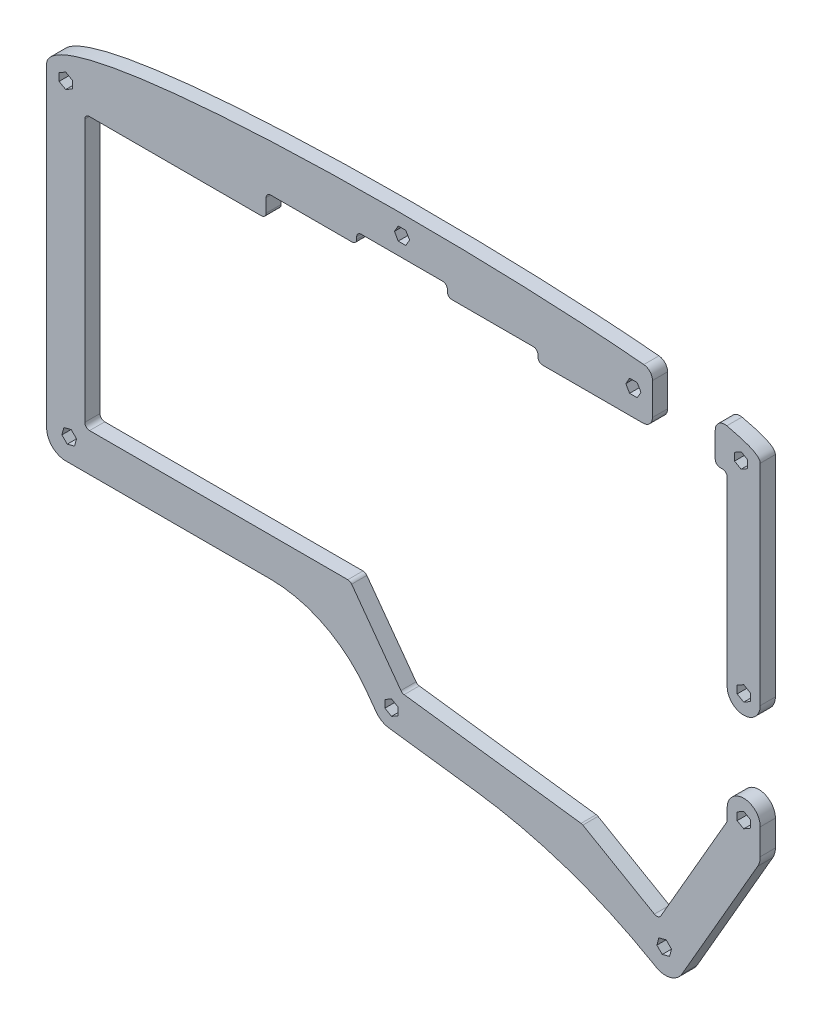
SolidWorks part; units mm, degrees
ref_plane "Front Plane" through (0, 0, 0) normal (0, 0, 1) x (1, 0, 0)
ref_plane "Top Plane" through (0, 0, 0) normal (0, 1, 0) x (1, 0, 0)
ref_plane "Right Plane" through (0, 0, 0) normal (1, 0, 0) x (0, 0, -1)
sketch "Model" plane through (0, 0, 0) normal (0, 0, 1) x (1, 0, 0)
  line L0 (-21.8431, 7.4481) -> (-8.6148, 30.3792)
  line L1 (-38.0636, 15.3297) -> (-23.771, 7.0696)
  line L2 (-75.3888, 20.2293) -> (-38.7189, 15.4592)
  line L3 (-86.2854, 34.8343) -> (-75.7419, 20.3766)
  line L4 (-29.1405, 92.9799) -> (-29.1405, 91.7303)
  line L5 (-8.8891, 91.2299) -> (-28.6402, 91.2299)
  line L6 (-8.3888, 90.7295) -> (-8.3888, 31.2555)
  line L7 (-86.6385, 34.9791) -> (-141.6396, 34.9791)
  line L8 (-142.1399, 90.7295) -> (-142.1399, 35.4795)
  line L9 (-104.6394, 91.2299) -> (-141.6396, 91.2299)
  line L10 (-104.139, 95.4793) -> (-104.139, 91.7303)
  line L11 (-85.6402, 95.9797) -> (-103.6387, 95.9797)
  line L12 (-85.1399, 97.7297) -> (-85.1399, 96.4801)
  line L13 (-67.6393, 98.2301) -> (-84.6395, 98.2301)
  line L14 (-67.1389, 96.4801) -> (-67.1389, 97.7297)
  line L15 (-48.6401, 95.9797) -> (-66.6385, 95.9797)
  line L16 (-48.1397, 93.9807) -> (-48.1397, 95.4793)
  line L17 (-29.6384, 93.4803) -> (-47.6393, 93.4803)
  line L18 (135.1563, 30.6526) -> (116.2359, 41.5721)
  line L19 (123.1828, 7.2669) -> (135.5373, 28.7222)
  line L20 (106.9623, 15.1485) -> (121.2549, 6.8884)
  line L21 (69.6371, 20.0481) -> (106.307, 15.278)
  line L22 (58.7405, 34.6531) -> (69.284, 20.1955)
  line L23 (115.8854, 92.7987) -> (115.8828, 42.2376)
  line L24 (58.3874, 34.7979) -> (3.3863, 34.7979)
  line L25 (2.886, 90.5483) -> (2.886, 35.2983)
  line L26 (40.3865, 91.0487) -> (3.3863, 91.0487)
  line L27 (40.8869, 95.2981) -> (40.8869, 91.5491)
  line L28 (59.3857, 95.7985) -> (41.3872, 95.7985)
  line L29 (59.886, 97.5485) -> (59.886, 96.2989)
  line L30 (77.3866, 98.0489) -> (60.3864, 98.0489)
  line L31 (77.887, 96.2989) -> (77.887, 97.5485)
  line L32 (96.3858, 95.7985) -> (78.3874, 95.7985)
  line L33 (96.8862, 93.7995) -> (96.8862, 95.2981)
  line L34 (115.3875, 93.2991) -> (97.3866, 93.2991)
  line L35 (20.1915, -96.2476) -> (6.9631, -73.3165)
  line L36 (36.4119, -88.366) -> (22.1193, -96.6261)
  line L37 (73.7371, -83.4663) -> (37.0672, -88.2365)
  line L38 (84.6337, -68.8614) -> (74.0902, -83.319)
  line L39 (27.4889, -10.7157) -> (27.4889, -11.9654)
  line L40 (7.2375, -12.4658) -> (26.9885, -12.4658)
  line L41 (6.7371, -12.9662) -> (6.7371, -72.4402)
  line L42 (84.9868, -68.7166) -> (139.9879, -68.7166)
  line L43 (140.4883, -12.9662) -> (140.4883, -68.2162)
  line L44 (102.9878, -12.4658) -> (139.9879, -12.4658)
  line L45 (102.4874, -8.2164) -> (102.4874, -11.9654)
  line L46 (83.9886, -7.716) -> (101.987, -7.716)
  line L47 (83.4882, -5.9659) -> (83.4882, -7.2156)
  line L48 (65.9876, -5.4656) -> (82.9878, -5.4656)
  line L49 (65.4872, -7.2156) -> (65.4872, -5.9659)
  line L50 (46.9884, -7.716) -> (64.9869, -7.716)
  line L51 (46.488, -9.715) -> (46.488, -8.2164)
  line L52 (27.9867, -10.2154) -> (45.9877, -10.2154)
  line L53 (-136.808, -73.043) -> (-117.8876, -62.1236)
  line L54 (-124.8344, -96.4288) -> (-137.189, -74.9734)
  line L55 (-108.614, -88.5472) -> (-122.9066, -96.8073)
  line L56 (-71.2888, -83.6475) -> (-107.9587, -88.4176)
  line L57 (-60.3922, -69.0425) -> (-70.9357, -83.5002)
  line L58 (-117.537, -10.8969) -> (-117.5345, -61.4581)
  line L59 (-60.0391, -68.8978) -> (-5.038, -68.8978)
  line L60 (-4.5376, -13.1474) -> (-4.5376, -68.3974)
  line L61 (-42.0381, -12.647) -> (-5.038, -12.647)
  line L62 (-42.5385, -8.3976) -> (-42.5385, -12.1466)
  line L63 (-61.0373, -7.8972) -> (-43.0389, -7.8972)
  line L64 (-61.5377, -6.1471) -> (-61.5377, -7.3968)
  line L65 (-79.0383, -5.6467) -> (-62.0381, -5.6467)
  line L66 (-79.5387, -7.3968) -> (-79.5387, -6.1471)
  line L67 (-98.0375, -7.8972) -> (-80.039, -7.8972)
  line L68 (-98.5378, -9.8962) -> (-98.5378, -8.3976)
  line L69 (-117.0392, -10.3965) -> (-99.0382, -10.3965)
  line L70 (138.9148, 92.1117) -> (138.9148, 33.3582)
  line L71 (138.1649, 32.9251) -> (119.446, 43.7282)
  line L72 (119.196, 44.1613) -> (119.196, 92.1092)
  line L73 (119.6959, 92.6092) -> (138.4148, 92.6117)
  line L74 (-140.5665, -11.584) -> (-140.5665, -70.3375)
  line L75 (-139.8166, -70.7706) -> (-121.0977, -59.9674)
  line L76 (-120.8476, -59.5344) -> (-120.8476, -11.5865)
  line L77 (-121.3476, -11.0865) -> (-140.0664, -11.084)
  line L78 (18.8966, 74.9256) -> (4.8966, 74.9256)
  line L79 (4.8966, 74.9256) -> (4.8966, 88.9256)
  line L80 (4.8966, 88.9256) -> (18.8966, 88.9256)
  line L81 (18.8966, 88.9256) -> (18.8966, 74.9256)
  line L82 (18.8966, 55.9256) -> (4.8966, 55.9256)
  line L83 (4.8966, 55.9256) -> (4.8966, 69.9256)
  line L84 (4.8966, 69.9256) -> (18.8966, 69.9256)
  line L85 (18.8966, 69.9256) -> (18.8966, 55.9256)
  line L86 (18.8966, 36.9256) -> (4.8966, 36.9256)
  line L87 (4.8966, 36.9256) -> (4.8966, 50.9256)
  line L88 (4.8966, 50.9256) -> (18.8966, 50.9256)
  line L89 (18.8966, 50.9256) -> (18.8966, 36.9256)
  line L90 (37.8948, 74.9262) -> (23.8948, 74.9262)
  line L91 (23.8948, 74.9262) -> (23.8948, 88.9262)
  line L92 (23.8948, 88.9262) -> (37.8948, 88.9262)
  line L93 (37.8948, 88.9262) -> (37.8948, 74.9262)
  line L94 (37.8948, 55.9262) -> (23.8948, 55.9262)
  line L95 (23.8948, 55.9262) -> (23.8948, 69.9262)
  line L96 (23.8948, 69.9262) -> (37.8948, 69.9262)
  line L97 (37.8948, 69.9262) -> (37.8948, 55.9262)
  line L98 (37.8948, 36.9262) -> (23.8948, 36.9262)
  line L99 (23.8948, 36.9262) -> (23.8948, 50.9262)
  line L100 (23.8948, 50.9262) -> (37.8948, 50.9262)
  line L101 (37.8948, 50.9262) -> (37.8948, 36.9262)
  line L102 (56.895, 79.671) -> (42.895, 79.671)
  line L103 (42.895, 79.671) -> (42.895, 93.671)
  line L104 (42.895, 93.671) -> (56.895, 93.671)
  line L105 (56.895, 93.671) -> (56.895, 79.671)
  line L106 (56.895, 60.6711) -> (42.895, 60.6711)
  line L107 (42.895, 60.6711) -> (42.895, 74.6711)
  line L108 (42.895, 74.6711) -> (56.895, 74.6711)
  line L109 (56.895, 74.6711) -> (56.895, 60.6711)
  line L110 (56.895, 41.6711) -> (42.895, 41.6711)
  line L111 (42.895, 41.6711) -> (42.895, 55.6711)
  line L112 (42.895, 55.6711) -> (56.895, 55.6711)
  line L113 (56.895, 55.6711) -> (56.895, 41.6711)
  line L114 (75.897, 82.0499) -> (61.897, 82.0499)
  line L115 (61.897, 82.0499) -> (61.897, 96.0499)
  line L116 (61.897, 96.0499) -> (75.897, 96.0499)
  line L117 (75.897, 96.0499) -> (75.897, 82.0499)
  line L118 (75.897, 63.0499) -> (61.897, 63.0499)
  line L119 (61.897, 63.0499) -> (61.897, 77.0499)
  line L120 (61.897, 77.0499) -> (75.897, 77.0499)
  line L121 (75.897, 77.0499) -> (75.897, 63.0499)
  line L122 (75.897, 44.0499) -> (61.897, 44.0499)
  line L123 (61.897, 44.0499) -> (61.897, 58.0499)
  line L124 (61.897, 58.0499) -> (75.897, 58.0499)
  line L125 (75.897, 58.0499) -> (75.897, 44.0499)
  line L126 (94.8982, 79.6753) -> (80.8982, 79.6753)
  line L127 (80.8982, 79.6753) -> (80.8982, 93.6753)
  line L128 (80.8982, 93.6753) -> (94.8982, 93.6753)
  line L129 (94.8982, 93.6753) -> (94.8982, 79.6753)
  line L130 (94.8982, 60.6753) -> (80.8982, 60.6753)
  line L131 (80.8982, 60.6753) -> (80.8982, 74.6753)
  line L132 (80.8982, 74.6753) -> (94.8982, 74.6753)
  line L133 (94.8982, 74.6753) -> (94.8982, 60.6753)
  line L134 (94.8982, 41.6753) -> (80.8982, 41.6753)
  line L135 (80.8982, 41.6753) -> (80.8982, 55.6753)
  line L136 (80.8982, 55.6753) -> (94.8982, 55.6753)
  line L137 (94.8982, 55.6753) -> (94.8982, 41.6753)
  line L138 (113.9, 77.2905) -> (99.9, 77.2905)
  line L139 (99.9, 77.2905) -> (99.9, 91.2905)
  line L140 (99.9, 91.2905) -> (113.9, 91.2905)
  line L141 (113.9, 91.2905) -> (113.9, 77.2905)
  line L142 (113.9, 58.2905) -> (99.9, 58.2905)
  line L143 (99.9, 58.2905) -> (99.9, 72.2905)
  line L144 (99.9, 72.2905) -> (113.9, 72.2905)
  line L145 (113.9, 72.2905) -> (113.9, 58.2905)
  line L146 (113.9, 39.2905) -> (99.9, 39.2905)
  line L147 (99.9, 39.2905) -> (99.9, 53.2905)
  line L148 (99.9, 53.2905) -> (113.9, 53.2905)
  line L149 (113.9, 53.2905) -> (113.9, 39.2905)
  line L150 (85.4166, 22.0174) -> (71.4166, 22.0174)
  line L151 (71.4166, 22.0174) -> (71.4166, 36.0174)
  line L152 (71.4166, 36.0174) -> (85.4166, 36.0174)
  line L153 (85.4166, 36.0174) -> (85.4166, 22.0174)
  line L154 (104.3289, 17.734) -> (90.806, 21.3575)
  line L155 (90.806, 21.3575) -> (94.4294, 34.8805)
  line L156 (94.4294, 34.8805) -> (107.9524, 31.257)
  line L157 (107.9524, 31.257) -> (104.3289, 17.734)
  line L158 (124.1994, 13.0049) -> (112.075, 20.0049)
  line L159 (112.075, 20.0049) -> (119.075, 32.1293)
  line L160 (119.075, 32.1293) -> (131.1994, 25.1293)
  line L161 (131.1994, 25.1293) -> (124.1994, 13.0049)
  line L162 (-20.5483, -28.7701) -> (-6.5483, -28.7701)
  line L163 (-6.5483, -28.7701) -> (-6.5483, -14.7701)
  line L164 (-6.5483, -14.7701) -> (-20.5483, -14.7701)
  line L165 (-20.5483, -14.7701) -> (-20.5483, -28.7701)
  line L166 (-20.5483, -47.7701) -> (-6.5483, -47.7701)
  line L167 (-6.5483, -47.7701) -> (-6.5483, -33.7701)
  line L168 (-6.5483, -33.7701) -> (-20.5483, -33.7701)
  line L169 (-20.5483, -33.7701) -> (-20.5483, -47.7701)
  line L170 (-20.5483, -66.7701) -> (-6.5483, -66.7701)
  line L171 (-6.5483, -66.7701) -> (-6.5483, -52.7701)
  line L172 (-6.5483, -52.7701) -> (-20.5483, -52.7701)
  line L173 (-20.5483, -52.7701) -> (-20.5483, -66.7701)
  line L174 (-39.5464, -28.7694) -> (-25.5464, -28.7694)
  line L175 (-25.5464, -28.7694) -> (-25.5464, -14.7694)
  line L176 (-25.5464, -14.7694) -> (-39.5464, -14.7694)
  line L177 (-39.5464, -14.7694) -> (-39.5464, -28.7694)
  line L178 (-39.5464, -47.7694) -> (-25.5464, -47.7694)
  line L179 (-25.5464, -47.7694) -> (-25.5464, -33.7694)
  line L180 (-25.5464, -33.7694) -> (-39.5464, -33.7694)
  line L181 (-39.5464, -33.7694) -> (-39.5464, -47.7694)
  line L182 (-39.5464, -66.7694) -> (-25.5464, -66.7694)
  line L183 (-25.5464, -66.7694) -> (-25.5464, -52.7694)
  line L184 (-25.5464, -52.7694) -> (-39.5464, -52.7694)
  line L185 (-39.5464, -52.7694) -> (-39.5464, -66.7694)
  line L186 (-58.5467, -24.0246) -> (-44.5467, -24.0246)
  line L187 (-44.5467, -24.0246) -> (-44.5467, -10.0246)
  line L188 (-44.5467, -10.0246) -> (-58.5467, -10.0246)
  line L189 (-58.5467, -10.0246) -> (-58.5467, -24.0246)
  line L190 (-58.5467, -43.0246) -> (-44.5467, -43.0246)
  line L191 (-44.5467, -43.0246) -> (-44.5467, -29.0246)
  line L192 (-44.5467, -29.0246) -> (-58.5467, -29.0246)
  line L193 (-58.5467, -29.0246) -> (-58.5467, -43.0246)
  line L194 (-58.5467, -62.0246) -> (-44.5467, -62.0246)
  line L195 (-44.5467, -62.0246) -> (-44.5467, -48.0246)
  line L196 (-44.5467, -48.0246) -> (-58.5467, -48.0246)
  line L197 (-58.5467, -48.0246) -> (-58.5467, -62.0246)
  line L198 (-77.5486, -21.6458) -> (-63.5486, -21.6458)
  line L199 (-63.5486, -21.6458) -> (-63.5486, -7.6458)
  line L200 (-63.5486, -7.6458) -> (-77.5486, -7.6458)
  line L201 (-77.5486, -7.6458) -> (-77.5486, -21.6458)
  line L202 (-77.5486, -40.6458) -> (-63.5486, -40.6458)
  line L203 (-63.5486, -40.6458) -> (-63.5486, -26.6458)
  line L204 (-63.5486, -26.6458) -> (-77.5486, -26.6458)
  line L205 (-77.5486, -26.6458) -> (-77.5486, -40.6458)
  line L206 (-77.5486, -59.6458) -> (-63.5486, -59.6458)
  line L207 (-63.5486, -59.6458) -> (-63.5486, -45.6458)
  line L208 (-63.5486, -45.6458) -> (-77.5486, -45.6458)
  line L209 (-77.5486, -45.6458) -> (-77.5486, -59.6458)
  line L210 (-96.5499, -24.0204) -> (-82.5499, -24.0204)
  line L211 (-82.5499, -24.0204) -> (-82.5499, -10.0204)
  line L212 (-82.5499, -10.0204) -> (-96.5499, -10.0204)
  line L213 (-96.5499, -10.0204) -> (-96.5499, -24.0204)
  line L214 (-96.5499, -43.0203) -> (-82.5499, -43.0203)
  line L215 (-82.5499, -43.0203) -> (-82.5499, -29.0203)
  line L216 (-82.5499, -29.0203) -> (-96.5499, -29.0203)
  line L217 (-96.5499, -29.0203) -> (-96.5499, -43.0203)
  line L218 (-96.5499, -62.0203) -> (-82.5499, -62.0203)
  line L219 (-82.5499, -62.0203) -> (-82.5499, -48.0203)
  line L220 (-82.5499, -48.0203) -> (-96.5499, -48.0203)
  line L221 (-96.5499, -48.0203) -> (-96.5499, -62.0203)
  line L222 (-115.5516, -26.4052) -> (-101.5516, -26.4052)
  line L223 (-101.5516, -26.4052) -> (-101.5516, -12.4052)
  line L224 (-101.5516, -12.4052) -> (-115.5516, -12.4052)
  line L225 (-115.5516, -12.4052) -> (-115.5516, -26.4052)
  line L226 (-115.5516, -45.4052) -> (-101.5516, -45.4052)
  line L227 (-101.5516, -45.4052) -> (-101.5516, -31.4052)
  line L228 (-101.5516, -31.4052) -> (-115.5516, -31.4052)
  line L229 (-115.5516, -31.4052) -> (-115.5516, -45.4052)
  line L230 (-115.5516, -64.4052) -> (-101.5516, -64.4052)
  line L231 (-101.5516, -64.4052) -> (-101.5516, -50.4052)
  line L232 (-101.5516, -50.4052) -> (-115.5516, -50.4052)
  line L233 (-115.5516, -50.4052) -> (-115.5516, -64.4052)
  line L234 (-87.0683, -81.6783) -> (-73.0683, -81.6783)
  line L235 (-73.0683, -81.6783) -> (-73.0683, -67.6783)
  line L236 (-73.0683, -67.6783) -> (-87.0683, -67.6783)
  line L237 (-87.0683, -67.6783) -> (-87.0683, -81.6783)
  line L238 (-105.9806, -85.9616) -> (-92.4576, -82.3382)
  line L239 (-92.4576, -82.3382) -> (-96.0811, -68.8152)
  line L240 (-96.0811, -68.8152) -> (-109.6041, -72.4387)
  line L241 (-109.6041, -72.4387) -> (-105.9806, -85.9616)
  line L242 (-125.851, -90.6908) -> (-113.7267, -83.6908)
  line L243 (-113.7267, -83.6908) -> (-120.7267, -71.5664)
  line L244 (-120.7267, -71.5664) -> (-132.851, -78.5664)
  line L245 (-132.851, -78.5664) -> (-125.851, -90.6908)
  spline S0 degree 3 poles (-8.6153, 30.3807) (-8.4626, 30.6458) (-8.3842, 30.9472) (-8.3882, 31.2532) knots 0 0 0 0 1 1 1 1
  spline S1 degree 3 poles (-21.8439, 7.4422) (-21.8429, 7.4437) (-21.8419, 7.4453) (-21.8408, 7.4468) knots 1 1 1 1 2 2 2 2
  spline S2 degree 3 poles (-23.769, 7.0673) (-23.1339, 6.6392) (-22.272, 6.8071) (-21.8439, 7.4422) knots 0 0 0 0 1 1 1 1
  spline S3 degree 3 poles (-38.063, 15.3284) (-38.2765, 15.3928) (-38.4957, 15.4362) (-38.7176, 15.4579) knots 0 0 0 0 1 1 1 1
  spline S4 degree 3 poles (-75.7416, 20.3746) (-75.6478, 20.2809) (-75.5206, 20.2283) (-75.3881, 20.2283) knots 0 0 0 0 1 1 1 1
  spline S5 degree 3 poles (-29.1383, 92.9782) (-29.1382, 93.2543) (-29.362, 93.4782) (-29.6381, 93.4783) knots 0 0 0 0 1 1 1 1
  spline S6 degree 3 poles (-29.1383, 91.7282) (-29.1383, 91.4521) (-28.9145, 91.2282) (-28.6384, 91.2281) (-28.6383, 91.2281) (-28.6382, 91.2281) (-28.6381, 91.2281) knots 0 0 0 0 1 1 1 2 2 2 2
  spline S7 degree 3 poles (-86.2846, 34.8318) (-86.3784, 34.9256) (-86.5056, 34.9783) (-86.6385, 34.9791) knots 0 0 0 0 1 1 1 1
  spline S8 degree 3 poles (-142.1382, 35.4782) (-142.1381, 35.2021) (-141.9142, 34.9783) (-141.6381, 34.9783) knots 0 0 0 0 1 1 1 1
  spline S9 degree 3 poles (-141.638, 91.2281) (-141.9142, 91.2282) (-142.1381, 91.0044) (-142.1382, 90.7282) knots 0 0 0 0 1 1 1 1
  spline S10 degree 3 poles (-104.6382, 91.2281) (-104.362, 91.228) (-104.1381, 91.4518) (-104.138, 91.728) (-104.138, 91.7281) (-104.138, 91.7281) (-104.138, 91.7282) knots 0 0 0 0 1 1 1 2 2 2 2
  spline S11 degree 3 poles (-103.6382, 95.9781) (-103.9142, 95.9781) (-104.138, 95.7543) (-104.138, 95.4783) knots 0 0 0 0 1 1 1 1
  spline S12 degree 3 poles (-85.6382, 95.9781) (-85.3621, 95.9781) (-85.1382, 96.2019) (-85.1381, 96.478) (-85.1381, 96.4781) (-85.1381, 96.4782) (-85.1381, 96.4783) knots 0 0 0 0 1 1 1 2 2 2 2
  spline S13 degree 3 poles (-84.6382, 98.2283) (-84.9144, 98.2283) (-85.1382, 98.0044) (-85.1381, 97.7282) knots 0 0 0 0 1 1 1 1
  spline S14 degree 3 poles (-67.1381, 97.7282) (-67.1381, 98.0043) (-67.3619, 98.2283) (-67.638, 98.2283) knots 0 0 0 0 2 2 2 2
  spline S15 degree 3 poles (-67.1381, 96.4783) (-67.1382, 96.2021) (-66.9144, 95.9782) (-66.6383, 95.9781) (-66.6382, 95.9781) (-66.6381, 95.9781) (-66.638, 95.9781) knots 0 0 0 0 1 1 1 2 2 2 2
  spline S16 degree 3 poles (-48.1382, 95.4783) (-48.1383, 95.7543) (-48.362, 95.9781) (-48.6381, 95.9781) knots 0 0 0 0 1 1 1 1
  spline S17 degree 3 poles (-48.1382, 93.9782) (-48.1381, 93.702) (-47.9142, 93.4782) (-47.6381, 93.4783) knots 0 0 0 0 1 1 1 1
  spline S18 degree 3 poles (-8.3882, 90.7282) (-8.3883, 91.0043) (-8.6121, 91.228) (-8.8881, 91.2281) knots 0 0 0 0 1 1 1 1
  spline S19 degree 3 poles (115.8851, 42.2368) (115.8929, 41.9725) (116.0232, 41.7268) (116.2377, 41.5721) knots 0 0 0 0 1 1 1 1
  spline S20 degree 3 poles (135.163, 30.647) (135.1614, 30.648) (135.1599, 30.6491) (135.1583, 30.6501) knots 1 1 1 1 2 2 2 2
  spline S21 degree 3 poles (135.5373, 28.7222) (135.9659, 29.3571) (135.7981, 30.2189) (135.163, 30.647) knots 0 0 0 0 1 1 1 1
  spline S22 degree 3 poles (123.182, 7.261) (123.183, 7.2625) (123.184, 7.2641) (123.1851, 7.2656) knots 1 1 1 1 2 2 2 2
  spline S23 degree 3 poles (121.2569, 6.8861) (121.892, 6.4581) (122.7539, 6.6259) (123.182, 7.261) knots 0 0 0 0 1 1 1 1
  spline S24 degree 3 poles (106.9629, 15.1472) (106.7494, 15.2117) (106.5302, 15.255) (106.3083, 15.2768) knots 0 0 0 0 1 1 1 1
  spline S25 degree 3 poles (69.2843, 20.1934) (69.3781, 20.0997) (69.5053, 20.0471) (69.6378, 20.0471) knots 0 0 0 0 1 1 1 1
  spline S26 degree 3 poles (115.8876, 92.797) (115.8877, 93.0731) (115.6639, 93.297) (115.3878, 93.2971) knots 0 0 0 0 1 1 1 1
  spline S27 degree 3 poles (58.7413, 34.6506) (58.6475, 34.7444) (58.5203, 34.7971) (58.3874, 34.7979) knots 0 0 0 0 1 1 1 1
  spline S28 degree 3 poles (2.8877, 35.297) (2.8878, 35.0209) (3.1117, 34.7971) (3.3878, 34.7971) knots 0 0 0 0 1 1 1 1
  spline S29 degree 3 poles (3.3879, 91.0469) (3.1117, 91.047) (2.8878, 90.8232) (2.8877, 90.547) knots 0 0 0 0 1 1 1 1
  spline S30 degree 3 poles (40.3877, 91.0469) (40.6639, 91.0468) (40.8878, 91.2706) (40.8879, 91.5468) (40.8879, 91.5469) (40.8879, 91.5469) (40.8879, 91.547) knots 0 0 0 0 1 1 1 2 2 2 2
  spline S31 degree 3 poles (41.3877, 95.797) (41.1117, 95.7969) (40.8879, 95.5731) (40.8879, 95.2971) knots 0 0 0 0 1 1 1 1
  spline S32 degree 3 poles (59.3877, 95.797) (59.6638, 95.7969) (59.8877, 96.0207) (59.8878, 96.2968) (59.8878, 96.2969) (59.8878, 96.297) (59.8878, 96.2971) knots 0 0 0 0 1 1 1 2 2 2 2
  spline S33 degree 3 poles (60.3877, 98.0471) (60.1115, 98.0471) (59.8877, 97.8232) (59.8878, 97.547) knots 0 0 0 0 1 1 1 1
  spline S34 degree 3 poles (77.8878, 97.547) (77.8878, 97.8232) (77.664, 98.0471) (77.3879, 98.0471) knots 0 0 0 0 2 2 2 2
  spline S35 degree 3 poles (77.8878, 96.2971) (77.8877, 96.0209) (78.1115, 95.797) (78.3876, 95.797) (78.3877, 95.797) (78.3878, 95.797) (78.3879, 95.797) knots 0 0 0 0 1 1 1 2 2 2 2
  spline S36 degree 3 poles (96.8877, 95.2971) (96.8876, 95.5731) (96.6639, 95.7969) (96.3878, 95.797) knots 0 0 0 0 1 1 1 1
  spline S37 degree 3 poles (96.8877, 93.797) (96.8878, 93.5208) (97.1117, 93.297) (97.3878, 93.2971) knots 0 0 0 0 1 1 1 1
  spline S38 degree 3 poles (6.9637, -73.315) (6.8109, -73.0499) (6.7325, -72.7484) (6.7366, -72.4425) knots 0 0 0 0 1 1 1 1
  spline S39 degree 3 poles (20.1923, -96.2535) (20.1912, -96.252) (20.1902, -96.2504) (20.1892, -96.2489) knots 1 1 1 1 2 2 2 2
  spline S40 degree 3 poles (22.1173, -96.6284) (21.4822, -97.0564) (20.6203, -96.8886) (20.1923, -96.2535) knots 0 0 0 0 1 1 1 1
  spline S41 degree 3 poles (36.4114, -88.3673) (36.6248, -88.3028) (36.844, -88.2594) (37.0659, -88.2377) knots 0 0 0 0 1 1 1 1
  spline S42 degree 3 poles (74.0899, -83.3211) (73.9962, -83.4148) (73.869, -83.4674) (73.7364, -83.4674) knots 0 0 0 0 1 1 1 1
  spline S43 degree 3 poles (27.4866, -10.7175) (27.4865, -10.4414) (27.7103, -10.2175) (27.9865, -10.2174) knots 0 0 0 0 1 1 1 1
  spline S44 degree 3 poles (27.4866, -11.9674) (27.4866, -12.2436) (27.2628, -12.4675) (26.9867, -12.4676) (26.9866, -12.4676) (26.9865, -12.4676) (26.9865, -12.4676) knots 0 0 0 0 1 1 1 2 2 2 2
  spline S45 degree 3 poles (84.633, -68.8639) (84.7267, -68.7701) (84.8539, -68.7174) (84.9868, -68.7166) knots 0 0 0 0 1 1 1 1
  spline S46 degree 3 poles (140.4865, -68.2175) (140.4864, -68.4936) (140.2625, -68.7174) (139.9864, -68.7173) knots 0 0 0 0 1 1 1 1
  spline S47 degree 3 poles (139.9864, -12.4676) (140.2625, -12.4675) (140.4864, -12.6913) (140.4865, -12.9674) knots 0 0 0 0 1 1 1 1
  spline S48 degree 3 poles (102.9865, -12.4676) (102.7103, -12.4676) (102.4864, -12.2438) (102.4864, -11.9677) (102.4864, -11.9676) (102.4864, -11.9675) (102.4864, -11.9674) knots 0 0 0 0 1 1 1 2 2 2 2
  spline S49 degree 3 poles (101.9865, -7.7175) (102.2625, -7.7176) (102.4863, -7.9413) (102.4864, -8.2174) knots 0 0 0 0 1 1 1 1
  spline S50 degree 3 poles (83.9865, -7.7175) (83.7104, -7.7176) (83.4865, -7.4938) (83.4864, -7.2176) (83.4864, -7.2176) (83.4864, -7.2175) (83.4864, -7.2174) knots 0 0 0 0 1 1 1 2 2 2 2
  spline S51 degree 3 poles (82.9865, -5.4673) (83.2627, -5.4674) (83.4865, -5.6913) (83.4864, -5.9675) knots 0 0 0 0 1 1 1 1
  spline S52 degree 3 poles (65.4865, -5.9675) (65.4864, -5.6913) (65.7102, -5.4674) (65.9863, -5.4673) knots 0 0 0 0 2 2 2 2
  spline S53 degree 3 poles (65.4865, -7.2174) (65.4865, -7.4935) (65.2627, -7.7174) (64.9866, -7.7175) (64.9865, -7.7175) (64.9864, -7.7175) (64.9863, -7.7175) knots 0 0 0 0 1 1 1 2 2 2 2
  spline S54 degree 3 poles (46.4865, -8.2174) (46.4866, -7.9413) (46.7103, -7.7176) (46.9864, -7.7175) knots 0 0 0 0 1 1 1 1
  spline S55 degree 3 poles (46.4865, -9.7175) (46.4865, -9.9937) (46.2625, -10.2175) (45.9864, -10.2174) knots 0 0 0 0 1 1 1 1
  spline S56 degree 3 poles (6.7366, -12.9674) (6.7366, -12.6914) (6.9604, -12.4676) (7.2365, -12.4676) knots 0 0 0 0 1 1 1 1
  spline S57 degree 3 poles (-117.5368, -61.4589) (-117.5446, -61.7232) (-117.6748, -61.9689) (-117.8893, -62.1236) knots 0 0 0 0 1 1 1 1
  spline S58 degree 3 poles (-136.8146, -73.0487) (-136.8131, -73.0476) (-136.8116, -73.0466) (-136.81, -73.0456) knots 1 1 1 1 2 2 2 2
  spline S59 degree 3 poles (-137.189, -74.9734) (-137.6176, -74.3386) (-137.4497, -73.4767) (-136.8146, -73.0487) knots 0 0 0 0 1 1 1 1
  spline S60 degree 3 poles (-124.8336, -96.4347) (-124.8347, -96.4331) (-124.8357, -96.4316) (-124.8367, -96.4301) knots 1 1 1 1 2 2 2 2
  spline S61 degree 3 poles (-122.9086, -96.8095) (-123.5437, -97.2376) (-124.4056, -97.0698) (-124.8336, -96.4347) knots 0 0 0 0 1 1 1 1
  spline S62 degree 3 poles (-108.6145, -88.5485) (-108.4011, -88.484) (-108.1819, -88.4406) (-107.96, -88.4189) knots 0 0 0 0 1 1 1 1
  spline S63 degree 3 poles (-70.936, -83.5022) (-71.0297, -83.596) (-71.1569, -83.6486) (-71.2895, -83.6485) knots 0 0 0 0 1 1 1 1
  spline S64 degree 3 poles (-117.5393, -10.8987) (-117.5394, -10.6226) (-117.3156, -10.3987) (-117.0394, -10.3986) knots 0 0 0 0 1 1 1 1
  spline S65 degree 3 poles (-60.3929, -69.0451) (-60.2992, -68.9513) (-60.172, -68.8986) (-60.0391, -68.8978) knots 0 0 0 0 1 1 1 1
  spline S66 degree 3 poles (-4.5394, -68.3987) (-4.5395, -68.6748) (-4.7634, -68.8986) (-5.0395, -68.8985) knots 0 0 0 0 1 1 1 1
  spline S67 degree 3 poles (-5.0395, -12.6488) (-4.7634, -12.6487) (-4.5395, -12.8725) (-4.5394, -13.1486) knots 0 0 0 0 1 1 1 1
  spline S68 degree 3 poles (-42.0394, -12.6488) (-42.3156, -12.6488) (-42.5395, -12.425) (-42.5395, -12.1489) (-42.5395, -12.1488) (-42.5395, -12.1487) (-42.5395, -12.1486) knots 0 0 0 0 1 1 1 2 2 2 2
  spline S69 degree 3 poles (-43.0394, -7.8987) (-42.7634, -7.8988) (-42.5396, -8.1225) (-42.5395, -8.3986) knots 0 0 0 0 1 1 1 1
  spline S70 degree 3 poles (-61.0394, -7.8987) (-61.3155, -7.8988) (-61.5394, -7.675) (-61.5395, -7.3988) (-61.5395, -7.3988) (-61.5395, -7.3987) (-61.5395, -7.3986) knots 0 0 0 0 1 1 1 2 2 2 2
  spline S71 degree 3 poles (-62.0394, -5.6485) (-61.7632, -5.6486) (-61.5394, -5.8725) (-61.5395, -6.1486) knots 0 0 0 0 1 1 1 1
  spline S72 degree 3 poles (-79.5394, -6.1486) (-79.5395, -5.8725) (-79.3157, -5.6486) (-79.0396, -5.6485) knots 0 0 0 0 2 2 2 2
  spline S73 degree 3 poles (-79.5394, -7.3986) (-79.5394, -7.6747) (-79.7632, -7.8986) (-80.0393, -7.8987) (-80.0394, -7.8987) (-80.0395, -7.8987) (-80.0396, -7.8987) knots 0 0 0 0 1 1 1 2 2 2 2
  spline S74 degree 3 poles (-98.5394, -8.3986) (-98.5393, -8.1225) (-98.3156, -7.8988) (-98.0395, -7.8987) knots 0 0 0 0 1 1 1 1
  spline S75 degree 3 poles (-98.5394, -9.8987) (-98.5394, -10.1748) (-98.7634, -10.3986) (-99.0395, -10.3986) knots 0 0 0 0 1 1 1 1
  spline S76 degree 3 poles (-123.6381, 52.6314) (-124.2456, 52.6314) (-124.7381, 53.1239) (-124.7381, 53.7314) (-124.7381, 54.3389) (-124.2456, 54.8314) (-123.6381, 54.8314) knots 2 2 2 2 3 3 3 4 4 4 4
  spline S77 degree 3 poles (-123.6381, 54.8314) (-123.0306, 54.8314) (-122.5381, 54.3389) (-122.5381, 53.7314) (-122.5381, 53.1239) (-123.0306, 52.6314) (-123.6381, 52.6314) knots 0 0 0 0 1 1 1 2 2 2 2
  spline S78 degree 3 poles (-123.6381, 71.3814) (-124.2456, 71.3814) (-124.7381, 71.8739) (-124.7381, 72.4814) (-124.7381, 73.0889) (-124.2456, 73.5814) (-123.6381, 73.5814) knots 2 2 2 2 3 3 3 4 4 4 4
  spline S79 degree 3 poles (-123.6381, 73.5814) (-123.0306, 73.5814) (-122.5381, 73.0889) (-122.5381, 72.4814) (-122.5381, 71.8739) (-123.0306, 71.3814) (-123.6381, 71.3814) knots 0 0 0 0 1 1 1 2 2 2 2
  spline S80 degree 3 poles (-47.6381, 75.1312) (-48.2456, 75.1312) (-48.7381, 75.6237) (-48.7381, 76.2312) (-48.7381, 76.8387) (-48.2456, 77.3312) (-47.6381, 77.3312) knots 2 2 2 2 3 3 3 4 4 4 4
  spline S81 degree 3 poles (-47.6381, 77.3312) (-47.0306, 77.3312) (-46.5381, 76.8387) (-46.5381, 76.2312) (-46.5381, 75.6237) (-47.0306, 75.1312) (-47.6381, 75.1312) knots 0 0 0 0 1 1 1 2 2 2 2
  spline S82 degree 3 poles (-80.388, 35.3813) (-80.9956, 35.3813) (-81.488, 35.8738) (-81.488, 36.4813) (-81.488, 37.0888) (-80.9956, 37.5813) (-80.388, 37.5813) knots 2 2 2 2 3 3 3 4 4 4 4
  spline S83 degree 3 poles (-80.388, 37.5813) (-79.7805, 37.5813) (-79.288, 37.0888) (-79.288, 36.4813) (-79.288, 35.8738) (-79.7805, 35.3813) (-80.388, 35.3813) knots 0 0 0 0 1 1 1 2 2 2 2
  spline S84 degree 3 poles (-33.8881, 27.6312) (-34.4956, 27.6312) (-34.9881, 28.1237) (-34.9881, 28.7312) (-34.9881, 29.3388) (-34.4956, 29.8312) (-33.8881, 29.8312) knots 2 2 2 2 3 3 3 4 4 4 4
  spline S85 degree 3 poles (-33.8881, 29.8312) (-33.2805, 29.8312) (-32.7881, 29.3388) (-32.7881, 28.7312) (-32.7881, 28.1237) (-33.2805, 27.6312) (-33.8881, 27.6312) knots 0 0 0 0 1 1 1 2 2 2 2
  spline S86 degree 3 poles (21.3878, 52.4502) (20.7803, 52.4502) (20.2878, 52.9427) (20.2878, 53.5502) (20.2878, 54.1578) (20.7803, 54.6502) (21.3878, 54.6502) knots 2 2 2 2 3 3 3 4 4 4 4
  spline S87 degree 3 poles (21.3878, 54.6502) (21.9953, 54.6502) (22.4878, 54.1578) (22.4878, 53.5502) (22.4878, 52.9427) (21.9953, 52.4502) (21.3878, 52.4502) knots 0 0 0 0 1 1 1 2 2 2 2
  spline S88 degree 3 poles (97.3878, 74.95) (96.7803, 74.95) (96.2878, 75.4425) (96.2878, 76.05) (96.2878, 76.6575) (96.7803, 77.15) (97.3878, 77.15) knots 2 2 2 2 3 3 3 4 4 4 4
  spline S89 degree 3 poles (97.3878, 77.15) (97.9953, 77.15) (98.4878, 76.6575) (98.4878, 76.05) (98.4878, 75.4425) (97.9953, 74.95) (97.3878, 74.95) knots 0 0 0 0 1 1 1 2 2 2 2
  spline S90 degree 3 poles (64.6379, 35.2001) (64.0303, 35.2001) (63.5379, 35.6926) (63.5379, 36.3001) (63.5379, 36.9076) (64.0303, 37.4001) (64.6379, 37.4001) knots 2 2 2 2 3 3 3 4 4 4 4
  spline S91 degree 3 poles (64.6379, 37.4001) (65.2454, 37.4001) (65.7379, 36.9076) (65.7379, 36.3001) (65.7379, 35.6926) (65.2454, 35.2001) (64.6379, 35.2001) knots 0 0 0 0 1 1 1 2 2 2 2
  spline S92 degree 3 poles (111.1378, 27.4501) (110.5303, 27.4501) (110.0378, 27.9425) (110.0378, 28.5501) (110.0378, 29.1576) (110.5303, 29.65) (111.1378, 29.65) knots 2 2 2 2 3 3 3 4 4 4 4
  spline S93 degree 3 poles (111.1378, 29.65) (111.7454, 29.65) (112.2378, 29.1576) (112.2378, 28.5501) (112.2378, 27.9425) (111.7454, 27.4501) (111.1378, 27.4501) knots 0 0 0 0 1 1 1 2 2 2 2
  spline S94 degree 3 poles (121.9864, -51.0642) (122.5939, -51.0642) (123.0864, -50.5718) (123.0864, -49.9642) (123.0864, -49.3567) (122.5939, -48.8642) (121.9864, -48.8642) knots 2 2 2 2 3 3 3 4 4 4 4
  spline S95 degree 3 poles (121.9864, -48.8642) (121.3789, -48.8642) (120.8864, -49.3567) (120.8864, -49.9642) (120.8864, -50.5718) (121.3789, -51.0642) (121.9864, -51.0642) knots 0 0 0 0 1 1 1 2 2 2 2
  spline S96 degree 3 poles (121.9864, -32.3142) (122.5939, -32.3142) (123.0864, -31.8218) (123.0864, -31.2142) (123.0864, -30.6067) (122.5939, -30.1142) (121.9864, -30.1142) knots 2 2 2 2 3 3 3 4 4 4 4
  spline S97 degree 3 poles (121.9864, -30.1142) (121.3789, -30.1142) (120.8864, -30.6067) (120.8864, -31.2142) (120.8864, -31.8218) (121.3789, -32.3142) (121.9864, -32.3142) knots 0 0 0 0 1 1 1 2 2 2 2
  spline S98 degree 3 poles (45.9864, -28.5644) (46.5939, -28.5644) (47.0864, -28.072) (47.0864, -27.4644) (47.0864, -26.8569) (46.5939, -26.3644) (45.9864, -26.3644) knots 2 2 2 2 3 3 3 4 4 4 4
  spline S99 degree 3 poles (45.9864, -26.3644) (45.3789, -26.3644) (44.8864, -26.8569) (44.8864, -27.4644) (44.8864, -28.072) (45.3789, -28.5644) (45.9864, -28.5644) knots 0 0 0 0 1 1 1 2 2 2 2
  spline S100 degree 3 poles (78.7364, -68.3144) (79.3439, -68.3144) (79.8364, -67.8219) (79.8364, -67.2144) (79.8364, -66.6069) (79.3439, -66.1144) (78.7364, -66.1144) knots 2 2 2 2 3 3 3 4 4 4 4
  spline S101 degree 3 poles (78.7364, -66.1144) (78.1288, -66.1144) (77.6364, -66.6069) (77.6364, -67.2144) (77.6364, -67.8219) (78.1288, -68.3144) (78.7364, -68.3144) knots 0 0 0 0 1 1 1 2 2 2 2
  spline S102 degree 3 poles (32.2364, -76.0644) (32.8439, -76.0644) (33.3364, -75.5719) (33.3364, -74.9644) (33.3364, -74.3569) (32.8439, -73.8644) (32.2364, -73.8644) knots 2 2 2 2 3 3 3 4 4 4 4
  spline S103 degree 3 poles (32.2364, -73.8644) (31.6289, -73.8644) (31.1364, -74.3569) (31.1364, -74.9644) (31.1364, -75.5719) (31.6289, -76.0644) (32.2364, -76.0644) knots 0 0 0 0 1 1 1 2 2 2 2
  spline S104 degree 3 poles (-23.0395, -51.2454) (-22.432, -51.2454) (-21.9395, -50.7529) (-21.9395, -50.1454) (-21.9395, -49.5379) (-22.432, -49.0454) (-23.0395, -49.0454) knots 2 2 2 2 3 3 3 4 4 4 4
  spline S105 degree 3 poles (-23.0395, -49.0454) (-23.647, -49.0454) (-24.1395, -49.5379) (-24.1395, -50.1454) (-24.1395, -50.7529) (-23.647, -51.2454) (-23.0395, -51.2454) knots 0 0 0 0 1 1 1 2 2 2 2
  spline S106 degree 3 poles (-99.0395, -28.7456) (-98.432, -28.7456) (-97.9395, -28.2531) (-97.9395, -27.6456) (-97.9395, -27.0381) (-98.432, -26.5456) (-99.0395, -26.5456) knots 2 2 2 2 3 3 3 4 4 4 4
  spline S107 degree 3 poles (-99.0395, -26.5456) (-99.647, -26.5456) (-100.1395, -27.0381) (-100.1395, -27.6456) (-100.1395, -28.2531) (-99.647, -28.7456) (-99.0395, -28.7456) knots 0 0 0 0 1 1 1 2 2 2 2
  spline S108 degree 3 poles (-66.2895, -68.4956) (-65.682, -68.4956) (-65.1895, -68.0031) (-65.1895, -67.3956) (-65.1895, -66.7881) (-65.682, -66.2956) (-66.2895, -66.2956) knots 2 2 2 2 3 3 3 4 4 4 4
  spline S109 degree 3 poles (-66.2895, -66.2956) (-66.8971, -66.2956) (-67.3895, -66.7881) (-67.3895, -67.3956) (-67.3895, -68.0031) (-66.8971, -68.4956) (-66.2895, -68.4956) knots 0 0 0 0 1 1 1 2 2 2 2
  spline S110 degree 3 poles (-112.7895, -76.2456) (-112.182, -76.2456) (-111.6895, -75.7531) (-111.6895, -75.1456) (-111.6895, -74.5381) (-112.182, -74.0456) (-112.7895, -74.0456) knots 2 2 2 2 3 3 3 4 4 4 4
  spline S111 degree 3 poles (-112.7895, -74.0456) (-113.397, -74.0456) (-113.8895, -74.5381) (-113.8895, -75.1456) (-113.8895, -75.7531) (-113.397, -76.2456) (-112.7895, -76.2456) knots 0 0 0 0 1 1 1 2 2 2 2
  spline S112 degree 3 poles (138.9148, 33.3582) (138.9148, 32.9733) (138.4982, 32.7327) (138.1649, 32.9251) knots 1 1 1 1 2 2 2 2
  spline S113 degree 3 poles (119.446, 43.7282) (119.2913, 43.8175) (119.196, 43.9826) (119.196, 44.1613) knots 3 3 3 3 4 4 4 4
  spline S114 degree 3 poles (119.196, 92.1092) (119.196, 92.3853) (119.4198, 92.6092) (119.6959, 92.6092) knots 5 5 5 5 6 6 6 6
  spline S115 degree 3 poles (138.4148, 92.6117) (138.6909, 92.6117) (138.9148, 92.3879) (138.9148, 92.1117) knots 7 7 7 7 8 8 8 8
  spline S116 degree 3 poles (-140.5665, -70.3375) (-140.5665, -70.7224) (-140.1499, -70.9629) (-139.8166, -70.7706) knots 1 1 1 1 2 2 2 2
  spline S117 degree 3 poles (-121.0977, -59.9674) (-120.943, -59.8781) (-120.8476, -59.7131) (-120.8476, -59.5344) knots 3 3 3 3 4 4 4 4
  spline S118 degree 3 poles (-120.8476, -11.5865) (-120.8476, -11.3103) (-121.0715, -11.0865) (-121.3476, -11.0865) knots 5 5 5 5 6 6 6 6
  spline S119 degree 3 poles (-140.0664, -11.084) (-140.3426, -11.0839) (-140.5665, -11.3078) (-140.5665, -11.584) knots 7 7 7 7 8 8 8 8
  spline S120 degree 3 poles (120.7443, 45.1272) (120.7443, 45.7347) (121.2368, 46.2272) (121.8443, 46.2272) (122.4518, 46.2272) (122.9443, 45.7347) (122.9443, 45.1272) knots 2 2 2 2 3 3 3 4 4 4 4
  spline S121 degree 3 poles (122.9443, 45.1272) (122.9443, 44.5197) (122.4518, 44.0272) (121.8443, 44.0272) (121.2368, 44.0272) (120.7443, 44.5197) (120.7443, 45.1272) knots 0 0 0 0 1 1 1 2 2 2 2
  spline S122 degree 3 poles (135.1763, 36.6063) (135.1763, 37.2138) (135.6688, 37.7063) (136.2763, 37.7063) (136.8838, 37.7063) (137.3763, 37.2138) (137.3763, 36.6063) knots 2 2 2 2 3 3 3 4 4 4 4
  spline S123 degree 3 poles (137.3763, 36.6063) (137.3763, 35.9988) (136.8838, 35.5063) (136.2763, 35.5063) (135.6688, 35.5063) (135.1763, 35.9988) (135.1763, 36.6063) knots 0 0 0 0 1 1 1 2 2 2 2
  spline S124 degree 3 poles (20.2878, 72.3002) (20.2878, 72.9078) (20.7803, 73.4002) (21.3878, 73.4002) (21.9953, 73.4002) (22.4878, 72.9078) (22.4878, 72.3002) knots 2 2 2 2 3 3 3 4 4 4 4
  spline S125 degree 3 poles (22.4878, 72.3002) (22.4878, 71.6927) (21.9953, 71.2002) (21.3878, 71.2002) (20.7803, 71.2002) (20.2878, 71.6927) (20.2878, 72.3002) knots 0 0 0 0 1 1 1 2 2 2 2
  spline S126 degree 3 poles (-122.3959, -58.5684) (-122.3959, -57.9609) (-122.8884, -57.4684) (-123.4959, -57.4684) (-124.1035, -57.4684) (-124.5959, -57.9609) (-124.5959, -58.5684) knots 2 2 2 2 3 3 3 4 4 4 4
  spline S127 degree 3 poles (-124.5959, -58.5684) (-124.5959, -59.1759) (-124.1035, -59.6684) (-123.4959, -59.6684) (-122.8884, -59.6684) (-122.3959, -59.1759) (-122.3959, -58.5684) knots 0 0 0 0 1 1 1 2 2 2 2
  spline S128 degree 3 poles (-136.8279, -67.0894) (-136.8279, -66.4818) (-137.3204, -65.9894) (-137.9279, -65.9894) (-138.5355, -65.9894) (-139.0279, -66.4818) (-139.0279, -67.0894) knots 2 2 2 2 3 3 3 4 4 4 4
  spline S129 degree 3 poles (-139.0279, -67.0894) (-139.0279, -67.6969) (-138.5355, -68.1894) (-137.9279, -68.1894) (-137.3204, -68.1894) (-136.8279, -67.6969) (-136.8279, -67.0894) knots 0 0 0 0 1 1 1 2 2 2 2
  spline S130 degree 3 poles (-21.9395, -31.3954) (-21.9395, -30.7879) (-22.432, -30.2954) (-23.0395, -30.2954) (-23.647, -30.2954) (-24.1395, -30.7879) (-24.1395, -31.3954) knots 2 2 2 2 3 3 3 4 4 4 4
  spline S131 degree 3 poles (-24.1395, -31.3954) (-24.1395, -32.0029) (-23.647, -32.4954) (-23.0395, -32.4954) (-22.432, -32.4954) (-21.9395, -32.0029) (-21.9395, -31.3954) knots 0 0 0 0 1 1 1 2 2 2 2
sketch "Sketch2" plane through (0, 0, 0) normal (0, 0, 1) x (1, 0, 0)
  line L0 (18.8966, 74.9256) -> (4.8966, 74.9256) construction
  line L1 (18.8966, 88.9256) -> (18.8966, 74.9256) construction
  line L2 (4.8966, 88.9256) -> (18.8966, 88.9256) construction
  line L3 (4.8966, 74.9256) -> (4.8966, 88.9256) construction
  line L4 (18.8966, 74.9256) -> (4.8966, 74.9256) construction
  line L5 (18.8966, 88.9256) -> (18.8966, 74.9256) construction
  line L6 (4.8966, 88.9256) -> (18.8966, 88.9256) construction
  line L7 (4.8966, 74.9256) -> (4.8966, 88.9256) construction
  line L8 (115.8854, 92.7987) -> (115.8828, 42.2376) construction
  line L9 (135.1563, 30.6526) -> (116.2359, 41.5721) construction
  line L10 (123.1828, 7.2669) -> (135.5373, 28.7222) construction
  line L11 (106.9623, 15.1485) -> (121.2549, 6.8884) construction
  line L12 (69.6371, 20.0481) -> (106.307, 15.278) construction
  line L13 (58.7405, 34.6531) -> (69.284, 20.1955) construction
  line L14 (85.4166, 36.0174) -> (85.4166, 22.0174) construction
  line L15 (85.4166, 22.0174) -> (71.4166, 22.0174) construction
  line L16 (71.4166, 22.0174) -> (71.4166, 36.0174) construction
  line L17 (71.4166, 36.0174) -> (85.4166, 36.0174) construction
  line L18 (107.9524, 31.257) -> (104.3289, 17.734) construction
  line L19 (104.3289, 17.734) -> (90.806, 21.3575) construction
  line L20 (90.806, 21.3575) -> (94.4294, 34.8805) construction
  line L21 (94.4294, 34.8805) -> (107.9524, 31.257) construction
  line L22 (112.075, 20.0049) -> (119.075, 32.1293) construction
  line L23 (119.075, 32.1293) -> (131.1994, 25.1293) construction
  line L24 (131.1994, 25.1293) -> (124.1994, 13.0049) construction
  line L25 (124.1994, 13.0049) -> (112.075, 20.0049) construction
  line L26 (99.9, 39.2905) -> (99.9, 53.2905) construction
  line L27 (99.9, 53.2905) -> (113.9, 53.2905) construction
  line L28 (113.9, 53.2905) -> (113.9, 39.2905) construction
  line L29 (113.9, 39.2905) -> (99.9, 39.2905) construction
  line L30 (80.8982, 41.6753) -> (80.8982, 55.6753) construction
  line L31 (80.8982, 55.6753) -> (94.8982, 55.6753) construction
  line L32 (94.8982, 55.6753) -> (94.8982, 41.6753) construction
  line L33 (94.8982, 41.6753) -> (80.8982, 41.6753) construction
  line L34 (58.3874, 34.7979) -> (3.3863, 34.7979) construction
  line L35 (61.897, 44.0499) -> (61.897, 58.0499) construction
  line L36 (61.897, 58.0499) -> (75.897, 58.0499) construction
  line L37 (75.897, 58.0499) -> (75.897, 44.0499) construction
  line L38 (75.897, 44.0499) -> (61.897, 44.0499) construction
  line L39 (42.895, 41.6711) -> (42.895, 55.6711) construction
  line L40 (42.895, 55.6711) -> (56.895, 55.6711) construction
  line L41 (56.895, 55.6711) -> (56.895, 41.6711) construction
  line L42 (56.895, 41.6711) -> (42.895, 41.6711) construction
  line L43 (23.8948, 36.9262) -> (23.8948, 50.9262) construction
  line L44 (23.8948, 50.9262) -> (37.8948, 50.9262) construction
  line L45 (37.8948, 50.9262) -> (37.8948, 36.9262) construction
  line L46 (37.8948, 36.9262) -> (23.8948, 36.9262) construction
  line L47 (18.8966, 50.9256) -> (18.8966, 36.9256) construction
  line L48 (18.8966, 36.9256) -> (4.8966, 36.9256) construction
  line L49 (4.8966, 36.9256) -> (4.8966, 50.9256) construction
  line L50 (4.8966, 50.9256) -> (18.8966, 50.9256) construction
  line L51 (99.9, 58.2905) -> (99.9, 72.2905) construction
  line L52 (99.9, 72.2905) -> (113.9, 72.2905) construction
  line L53 (113.9, 72.2905) -> (113.9, 58.2905) construction
  line L54 (113.9, 58.2905) -> (99.9, 58.2905) construction
  line L55 (94.8982, 74.6753) -> (94.8982, 60.6753) construction
  line L56 (94.8982, 60.6753) -> (80.8982, 60.6753) construction
  line L57 (80.8982, 60.6753) -> (80.8982, 74.6753) construction
  line L58 (80.8982, 74.6753) -> (94.8982, 74.6753) construction
  line L59 (61.897, 63.0499) -> (61.897, 77.0499) construction
  line L60 (61.897, 77.0499) -> (75.897, 77.0499) construction
  line L61 (75.897, 77.0499) -> (75.897, 63.0499) construction
  line L62 (75.897, 63.0499) -> (61.897, 63.0499) construction
  line L63 (42.895, 60.6711) -> (42.895, 74.6711) construction
  line L64 (42.895, 74.6711) -> (56.895, 74.6711) construction
  line L65 (56.895, 74.6711) -> (56.895, 60.6711) construction
  line L66 (56.895, 60.6711) -> (42.895, 60.6711) construction
  line L67 (23.8948, 55.9262) -> (23.8948, 69.9262) construction
  line L68 (23.8948, 69.9262) -> (37.8948, 69.9262) construction
  line L69 (37.8948, 69.9262) -> (37.8948, 55.9262) construction
  line L70 (37.8948, 55.9262) -> (23.8948, 55.9262) construction
  line L71 (4.8966, 55.9256) -> (4.8966, 69.9256) construction
  line L72 (4.8966, 69.9256) -> (18.8966, 69.9256) construction
  line L73 (18.8966, 69.9256) -> (18.8966, 55.9256) construction
  line L74 (18.8966, 55.9256) -> (4.8966, 55.9256) construction
  line L75 (99.9, 77.2905) -> (99.9, 91.2905) construction
  line L76 (99.9, 91.2905) -> (113.9, 91.2905) construction
  line L77 (113.9, 91.2905) -> (113.9, 77.2905) construction
  line L78 (113.9, 77.2905) -> (99.9, 77.2905) construction
  line L79 (80.8982, 79.6753) -> (80.8982, 93.6753) construction
  line L80 (80.8982, 93.6753) -> (94.8982, 93.6753) construction
  line L81 (94.8982, 93.6753) -> (94.8982, 79.6753) construction
  line L82 (94.8982, 79.6753) -> (80.8982, 79.6753) construction
  line L83 (61.897, 82.0499) -> (61.897, 96.0499) construction
  line L84 (61.897, 96.0499) -> (75.897, 96.0499) construction
  line L85 (75.897, 96.0499) -> (75.897, 82.0499) construction
  line L86 (75.897, 82.0499) -> (61.897, 82.0499) construction
  line L87 (2.886, 90.5483) -> (2.886, 35.2983) construction
  line L88 (42.895, 79.671) -> (42.895, 93.671) construction
  line L89 (42.895, 93.671) -> (56.895, 93.671) construction
  line L90 (56.895, 93.671) -> (56.895, 79.671) construction
  line L91 (56.895, 79.671) -> (42.895, 79.671) construction
  line L92 (23.8948, 88.9262) -> (37.8948, 88.9262) construction
  line L93 (37.8948, 88.9262) -> (37.8948, 74.9262) construction
  line L94 (37.8948, 74.9262) -> (23.8948, 74.9262) construction
  line L95 (23.8948, 74.9262) -> (23.8948, 88.9262) construction
  line L96 (115.8854, 92.7987) -> (115.8828, 42.2376) construction
  line L97 (135.1563, 30.6526) -> (116.2359, 41.5721) construction
  line L98 (123.1828, 7.2669) -> (135.5373, 28.7222) construction
  line L99 (106.9623, 15.1485) -> (121.2549, 6.8884) construction
  line L100 (69.6371, 20.0481) -> (106.307, 15.278) construction
  line L101 (58.7405, 34.6531) -> (69.284, 20.1955) construction
  line L102 (85.4166, 36.0174) -> (85.4166, 22.0174) construction
  line L103 (85.4166, 22.0174) -> (71.4166, 22.0174) construction
  line L104 (71.4166, 22.0174) -> (71.4166, 36.0174) construction
  line L105 (71.4166, 36.0174) -> (85.4166, 36.0174) construction
  line L106 (107.9524, 31.257) -> (104.3289, 17.734) construction
  line L107 (104.3289, 17.734) -> (90.806, 21.3575) construction
  line L108 (90.806, 21.3575) -> (94.4294, 34.8805) construction
  line L109 (94.4294, 34.8805) -> (107.9524, 31.257) construction
  line L110 (112.075, 20.0049) -> (119.075, 32.1293) construction
  line L111 (119.075, 32.1293) -> (131.1994, 25.1293) construction
  line L112 (131.1994, 25.1293) -> (124.1994, 13.0049) construction
  line L113 (124.1994, 13.0049) -> (112.075, 20.0049) construction
  line L114 (99.9, 39.2905) -> (99.9, 53.2905) construction
  line L115 (99.9, 53.2905) -> (113.9, 53.2905) construction
  line L116 (113.9, 53.2905) -> (113.9, 39.2905) construction
  line L117 (113.9, 39.2905) -> (99.9, 39.2905) construction
  line L118 (80.8982, 41.6753) -> (80.8982, 55.6753) construction
  line L119 (80.8982, 55.6753) -> (94.8982, 55.6753) construction
  line L120 (94.8982, 55.6753) -> (94.8982, 41.6753) construction
  line L121 (94.8982, 41.6753) -> (80.8982, 41.6753) construction
  line L122 (58.3874, 34.7979) -> (3.3863, 34.7979) construction
  line L123 (61.897, 44.0499) -> (61.897, 58.0499) construction
  line L124 (61.897, 58.0499) -> (75.897, 58.0499) construction
  line L125 (75.897, 58.0499) -> (75.897, 44.0499) construction
  line L126 (75.897, 44.0499) -> (61.897, 44.0499) construction
  line L127 (42.895, 41.6711) -> (42.895, 55.6711) construction
  line L128 (42.895, 55.6711) -> (56.895, 55.6711) construction
  line L129 (56.895, 55.6711) -> (56.895, 41.6711) construction
  line L130 (56.895, 41.6711) -> (42.895, 41.6711) construction
  line L131 (23.8948, 36.9262) -> (23.8948, 50.9262) construction
  line L132 (23.8948, 50.9262) -> (37.8948, 50.9262) construction
  line L133 (37.8948, 50.9262) -> (37.8948, 36.9262) construction
  line L134 (37.8948, 36.9262) -> (23.8948, 36.9262) construction
  line L135 (18.8966, 50.9256) -> (18.8966, 36.9256) construction
  line L136 (18.8966, 36.9256) -> (4.8966, 36.9256) construction
  line L137 (4.8966, 36.9256) -> (4.8966, 50.9256) construction
  line L138 (4.8966, 50.9256) -> (18.8966, 50.9256) construction
  line L139 (99.9, 58.2905) -> (99.9, 72.2905) construction
  line L140 (99.9, 72.2905) -> (113.9, 72.2905) construction
  line L141 (113.9, 72.2905) -> (113.9, 58.2905) construction
  line L142 (113.9, 58.2905) -> (99.9, 58.2905) construction
  line L143 (94.8982, 74.6753) -> (94.8982, 60.6753) construction
  line L144 (94.8982, 60.6753) -> (80.8982, 60.6753) construction
  line L145 (80.8982, 60.6753) -> (80.8982, 74.6753) construction
  line L146 (80.8982, 74.6753) -> (94.8982, 74.6753) construction
  line L147 (61.897, 63.0499) -> (61.897, 77.0499) construction
  line L148 (61.897, 77.0499) -> (75.897, 77.0499) construction
  line L149 (75.897, 77.0499) -> (75.897, 63.0499) construction
  line L150 (75.897, 63.0499) -> (61.897, 63.0499) construction
  line L151 (42.895, 60.6711) -> (42.895, 74.6711) construction
  line L152 (42.895, 74.6711) -> (56.895, 74.6711) construction
  line L153 (56.895, 74.6711) -> (56.895, 60.6711) construction
  line L154 (56.895, 60.6711) -> (42.895, 60.6711) construction
  line L155 (23.8948, 55.9262) -> (23.8948, 69.9262) construction
  line L156 (23.8948, 69.9262) -> (37.8948, 69.9262) construction
  line L157 (37.8948, 69.9262) -> (37.8948, 55.9262) construction
  line L158 (37.8948, 55.9262) -> (23.8948, 55.9262) construction
  line L159 (4.8966, 55.9256) -> (4.8966, 69.9256) construction
  line L160 (4.8966, 69.9256) -> (18.8966, 69.9256) construction
  line L161 (18.8966, 69.9256) -> (18.8966, 55.9256) construction
  line L162 (18.8966, 55.9256) -> (4.8966, 55.9256) construction
  line L163 (99.9, 77.2905) -> (99.9, 91.2905) construction
  line L164 (99.9, 91.2905) -> (113.9, 91.2905) construction
  line L165 (113.9, 91.2905) -> (113.9, 77.2905) construction
  line L166 (113.9, 77.2905) -> (99.9, 77.2905) construction
  line L167 (80.8982, 79.6753) -> (80.8982, 93.6753) construction
  line L168 (80.8982, 93.6753) -> (94.8982, 93.6753) construction
  line L169 (94.8982, 93.6753) -> (94.8982, 79.6753) construction
  line L170 (94.8982, 79.6753) -> (80.8982, 79.6753) construction
  line L171 (61.897, 82.0499) -> (61.897, 96.0499) construction
  line L172 (61.897, 96.0499) -> (75.897, 96.0499) construction
  line L173 (75.897, 96.0499) -> (75.897, 82.0499) construction
  line L174 (75.897, 82.0499) -> (61.897, 82.0499) construction
  line L175 (2.886, 90.5483) -> (2.886, 35.2983) construction
  line L176 (42.895, 79.671) -> (42.895, 93.671) construction
  line L177 (42.895, 93.671) -> (56.895, 93.671) construction
  line L178 (56.895, 93.671) -> (56.895, 79.671) construction
  line L179 (56.895, 79.671) -> (42.895, 79.671) construction
  line L180 (23.8948, 88.9262) -> (37.8948, 88.9262) construction
  line L181 (37.8948, 88.9262) -> (37.8948, 74.9262) construction
  line L182 (37.8948, 74.9262) -> (23.8948, 74.9262) construction
  line L183 (23.8948, 74.9262) -> (23.8948, 88.9262) construction
  line L184 (115.3875, 93.2991) -> (97.3866, 93.2991) construction
  line L185 (96.3858, 95.7985) -> (78.3874, 95.7985) construction
  line L186 (59.3857, 95.7985) -> (41.3872, 95.7985) construction
  line L187 (40.3865, 91.0487) -> (3.3863, 91.0487) construction
  line L188 (77.3866, 98.0489) -> (60.3864, 98.0489) construction
  line L189 (115.3875, 93.2991) -> (97.3866, 93.2991) construction
  line L190 (96.3858, 95.7985) -> (78.3874, 95.7985) construction
  line L191 (59.3857, 95.7985) -> (41.3872, 95.7985) construction
  line L192 (40.3865, 91.0487) -> (3.3863, 91.0487) construction
  line L193 (77.3866, 98.0489) -> (60.3864, 98.0489) construction
  line L194 (96.8862, 93.7995) -> (96.8862, 95.2981) construction
  line L195 (77.887, 96.2989) -> (77.887, 97.5485) construction
  line L196 (59.886, 97.5485) -> (59.886, 96.2989) construction
  line L197 (40.8869, 95.2981) -> (40.8869, 91.5491) construction
  line L198 (96.8862, 93.7995) -> (96.8862, 95.2981) construction
  line L199 (77.887, 96.2989) -> (77.887, 97.5485) construction
  line L200 (59.886, 97.5485) -> (59.886, 96.2989) construction
  line L201 (40.8869, 95.2981) -> (40.8869, 91.5491) construction
  line L202 (2.3966, 90.4634) -> (2.3966, 35.4256)
  line L203 (3.3966, 34.4256) -> (57.5361, 34.4256)
  line L204 (58.3441, 34.0148) -> (68.6635, 19.8644)
  line L205 (69.3425, 19.462) -> (106.4347, 14.637)
  line L207 (123.1646, 6.2126) -> (136.9265, 30.049)
  line L208 (137.0605, 30.2811) -> (116.8812, 41.9271) construction
  line L209 (116.4, 42.7604) -> (116.4, 92.8283) construction
  line L210 (115.4378, 93.7905) -> (98.3603, 93.7905)
  line L211 (97.3982, 94.7526) -> (97.3982, 95.2132)
  line L212 (96.4361, 96.1753) -> (79.3591, 96.1753)
  line L213 (78.397, 97.1374) -> (78.397, 97.5878)
  line L214 (77.4348, 98.5499) -> (60.3591, 98.5499)
  line L215 (59.397, 97.5878) -> (59.397, 97.1332)
  line L216 (58.4348, 96.171) -> (41.3572, 96.171)
  line L217 (40.395, 95.2089) -> (40.395, 92.3877)
  line L218 (39.4329, 91.4256) -> (3.3587, 91.4256)
  line L219 (40.3948, 39.1711) -> (59.395, 39.1711) construction
  line L221 (68.9166, 41.5499) -> (68.9166, 19.5174) construction
  line L222 (68.9166, 19.5174) -> (88.014, 19.5174) construction
  line L224 (59.395, 39.1711) -> (59.395, 41.5499) construction
  line L225 (59.395, 41.5499) -> (68.9166, 41.5499) construction
  line L226 (88.014, 19.5174) -> (106.0967, 14.6722) construction
  line L227 (106.0967, 14.6722) -> (107.4652, 19.7796) construction
  line L228 (106.8061, 14.5111) -> (121.7982, 5.8468)
  line L229 (20.2878, 72.3002) -> (22.4878, 72.3002) construction
  line L230 (-5.6034, 96.4256) -> (-5.6034, 30.4256)
  line L231 (21.3878, 54.6502) -> (21.3878, 52.4502) construction
  line L232 (-1.6034, 26.4256) -> (41.2672, 26.4256)
  line L233 (64.6379, 37.4001) -> (64.6379, 35.2001) construction
  line L234 (61.4664, 16.1562) -> (63.4651, 13.4155)
  line L235 (111.1378, 27.4501) -> (111.1378, 29.65) construction
  line L236 (66.181, 11.8059) -> (84.1879, 9.4635)
  line L237 (97.3878, 74.95) -> (97.3878, 77.15) construction
  line L238 (121.3259, -3.1202) -> (122.1261, -3.5826)
  line L239 (127.5917, -2.1194) -> (143.4535, 25.354)
  line L240 (143.9894, 27.354) -> (143.9894, 98.7905)
  line L241 (-5.6034, 90.4634) -> (-5.6034, 26.4256) construction
  line L242 (68.7843, 106.5499) -> (155.8423, 106.5499) construction
  line L243 (68.897, 106.5499) -> (68.897, 98.5499) construction
  line L244 (-5.6034, 96.4256) -> (-5.6034, 106.5499) construction
  line L245 (-5.6034, 101.4877) -> (-6.8515, 101.4877) construction
  line L246 (143.9894, 98.7905) -> (143.9894, 106.5499) construction
  line L247 (143.9894, 106.5499) -> (143.9894, 102.6702) construction
  line L248 (143.9894, 102.6702) -> (149.1856, 102.6702) construction
  line L249 (53.9773, 26.4256) -> (64.4774, 12.0275) construction
  line L250 (-5.6034, 26.4256) -> (53.9773, 26.4256) construction
  line L251 (101.2091, 8.5059) -> (125.5908, -5.585) construction
  line L252 (64.4774, 12.0275) -> (105.6011, 6.678) construction
  line L253 (125.5908, -5.585) -> (143.9887, 26.2811) construction
  line L254 (2.3966, 90.4634) -> (2.3966, 34.4256) construction
  line L255 (2.3966, 34.4256) -> (58.0445, 34.4256) construction
  line L256 (58.0445, 34.4256) -> (68.9166, 19.5174) construction
  line L257 (68.9166, 19.5174) -> (106.633, 14.6112) construction
  line L258 (105.2121, 15.4324) -> (122.6644, 5.3462) construction
  line L259 (122.6644, 5.3462) -> (137.0605, 30.2811) construction
  line L260 (122.5572, 5.7466) -> (125.162, -3.9833) construction
  line L261 (68.9616, 19.5934) -> (64.6575, 12.3314) construction
  line L262 (124.982, -0.2413) -> (125.3933, 1.2923)
  line L263 (125.3933, 1.2923) -> (124.2709, 2.4152)
  line L264 (124.2709, 2.4152) -> (122.7372, 2.0046)
  line L265 (122.7372, 2.0046) -> (122.3259, 0.4711)
  line L266 (122.3259, 0.4711) -> (123.4483, -0.6519)
  line L267 (123.4483, -0.6519) -> (124.982, -0.2413)
  line L268 (2.6895, 34.7185) -> (-4.4318, 27.5971) construction
  line L269 (66.6788, 14.1848) -> (68.0628, 14.9629)
  line L270 (68.0628, 14.9629) -> (68.081, 16.5505)
  line L271 (68.081, 16.5505) -> (66.7151, 17.3601)
  line L272 (66.7151, 17.3601) -> (65.3311, 16.582)
  line L273 (65.3311, 16.582) -> (65.313, 14.9944)
  line L274 (65.313, 14.9944) -> (66.6788, 14.1848)
  line L275 (143.4535, 25.354) -> (143.9894, 26.2822) construction
  line L276 (-1.2821, 29.6242) -> (0.2515, 30.0351)
  line L277 (0.2515, 30.0351) -> (0.6624, 31.5687)
  line L278 (0.6624, 31.5687) -> (-0.4602, 32.6914)
  line L279 (-0.4602, 32.6914) -> (-1.9939, 32.2805)
  line L280 (-1.9939, 32.2805) -> (-2.4048, 30.7469)
  line L281 (-2.4048, 30.7469) -> (-1.2821, 29.6242)
  line L282 (-1.6034, 93.8378) -> (-0.2284, 94.6317)
  line L283 (-0.2284, 94.6317) -> (-0.2284, 96.2194)
  line L284 (-0.2284, 96.2194) -> (-1.6034, 97.0133)
  line L285 (-1.6034, 97.0133) -> (-2.9784, 96.2194)
  line L286 (-2.9784, 96.2194) -> (-2.9784, 94.6317)
  line L287 (-2.9784, 94.6317) -> (-1.6034, 93.8378)
  line L288 (137.0605, 30.2811) -> (143.9894, 26.2822) construction
  line L289 (143.9894, 27.354) -> (143.9894, 26.2822) construction
  line L290 (137.0605, 30.2811) -> (143.9894, 30.2811) construction
  line L291 (69.6908, 101.1749) -> (70.4847, 102.5499)
  line L292 (70.4847, 102.5499) -> (69.6908, 103.9249)
  line L293 (69.6908, 103.9249) -> (68.1031, 103.9249)
  line L294 (68.1031, 103.9249) -> (67.3093, 102.5499)
  line L295 (67.3093, 102.5499) -> (68.1031, 101.1749)
  line L296 (68.1031, 101.1749) -> (69.6908, 101.1749)
  line L297 (140.5249, 30.6934) -> (141.8999, 31.4872)
  line L298 (141.8999, 31.4872) -> (141.8999, 33.0749)
  line L299 (141.8999, 33.0749) -> (140.5249, 33.8688)
  line L300 (140.5249, 33.8688) -> (139.1499, 33.0749)
  line L301 (139.1499, 33.0749) -> (139.1499, 31.4872)
  line L302 (139.1499, 31.4872) -> (140.5249, 30.6934)
  line L303 (121.4, 102.5131) -> (121.4, 95.7905)
  line L304 (140.5249, 53.6934) -> (141.8999, 54.4872)
  line L305 (141.8999, 54.4872) -> (141.8999, 56.0749)
  line L306 (141.8999, 56.0749) -> (140.5249, 56.8688)
  line L307 (140.5249, 56.8688) -> (139.1499, 56.0749)
  line L308 (139.1499, 56.0749) -> (139.1499, 54.4872)
  line L309 (139.1499, 54.4872) -> (140.5249, 53.6934)
  line L310 (139.9894, 95.7028) -> (141.3644, 96.4966)
  line L311 (141.3644, 96.4966) -> (141.3644, 98.0843)
  line L312 (141.3644, 98.0843) -> (139.9894, 98.8782)
  line L313 (139.9894, 98.8782) -> (138.6144, 98.0843)
  line L314 (138.6144, 98.0843) -> (138.6144, 96.4966)
  line L315 (138.6144, 96.4966) -> (139.9894, 95.7028)
  line L316 (118.1938, 97.7905) -> (118.9877, 99.1655)
  line L317 (118.9877, 99.1655) -> (118.1938, 100.5405)
  line L318 (118.1938, 100.5405) -> (116.6061, 100.5405)
  line L319 (116.6061, 100.5405) -> (115.8122, 99.1655)
  line L320 (115.8122, 99.1655) -> (116.6061, 97.7905)
  line L321 (116.6061, 97.7905) -> (118.1938, 97.7905)
  line L322 (137.0605, 30.549) -> (137.0605, 32.7811)
  line L323 (137.0605, 54.7811) -> (137.0605, 92.7905)
  line L324 (115.4378, 93.7905) -> (119.4, 93.7905)
  line L325 (135.5605, 93.7905) -> (136.0605, 93.7905)
  line L326 (134.5605, 94.7905) -> (134.5605, 100.1371)
  circle A0 centre (21.3878, 72.3002) radius 1.2
  circle A1 centre (21.3878, 53.5502) radius 1.2
  circle A2 centre (64.6379, 36.3001) radius 1.2
  circle A3 centre (111.1378, 28.5501) radius 1.2
  circle A4 centre (97.3878, 76.05) radius 1.2
  arc A11 (116.8812, 41.9271) -> (116.4, 42.7604) centre (117.3621, 42.7604) cw construction
  arc A12 (116.4, 92.8283) -> (115.4378, 93.7905) centre (115.4378, 92.8283) ccw construction
  arc A13 (98.3603, 93.7905) -> (97.3982, 94.7526) centre (98.3603, 94.7526) cw
  arc A14 (97.3982, 95.2132) -> (96.4361, 96.1753) centre (96.4361, 95.2132) ccw
  arc A15 (79.3591, 96.1753) -> (78.397, 97.1374) centre (79.3591, 97.1374) cw
  arc A16 (78.397, 97.5878) -> (77.4348, 98.5499) centre (77.4348, 97.5878) ccw
  arc A17 (59.397, 97.5878) -> (60.3591, 98.5499) centre (60.3591, 97.5878) cw
  arc A18 (59.397, 97.1332) -> (58.4348, 96.171) centre (58.4348, 97.1332) cw
  arc A19 (41.3572, 96.171) -> (40.395, 95.2089) centre (41.3572, 95.2089) ccw
  arc A20 (40.395, 92.3877) -> (39.4329, 91.4256) centre (39.4329, 92.3877) cw
  arc A21 (2.3966, 90.4634) -> (3.3587, 91.4256) centre (3.3587, 90.4634) cw
  arc A22 (61.4664, 16.1562) -> (41.2672, 26.4256) centre (41.2672, 1.4256) ccw
  arc A24 (143.9894, 27.354) -> (143.4535, 25.354) centre (139.9894, 27.354) cw
  arc A25 (-1.6034, 26.4256) -> (-5.6034, 30.4256) centre (-1.6034, 30.4256) cw
  arc A26 (66.181, 11.8059) -> (63.4651, 13.4155) centre (66.697, 15.7724) cw
  arc A27 (127.5917, -2.1194) -> (122.1261, -3.5826) centre (124.1276, -0.1194) cw
  arc A28 (2.3966, 35.4256) -> (3.3966, 34.4256) centre (3.3966, 35.4256) ccw
  arc A29 (68.6635, 19.8644) -> (69.3425, 19.462) centre (69.4715, 20.4537) ccw
  arc A30 (121.7982, 5.8468) -> (123.1646, 6.2126) centre (122.2985, 6.7126) ccw
  circle A31 centre (123.8596, 0.8817) radius 1.375 construction
  circle A32 centre (66.697, 15.7724) radius 1.375 construction
  circle A33 centre (-0.8712, 31.1578) radius 1.375 construction
  circle A34 centre (-1.6034, 95.4256) radius 1.375 construction
  circle A35 centre (68.897, 102.5499) radius 1.375 construction
  arc A36 (106.8061, 14.5111) -> (106.4347, 14.637) centre (106.3058, 13.6453) ccw
  arc A37 (121.3259, -3.1202) -> (84.1879, 9.4635) centre (71.2884, -89.701) ccw
  circle A38 centre (140.5249, 32.2811) radius 1.375 construction
  circle A39 centre (140.5249, 55.2811) radius 1.375 construction
  arc A40 (143.9894, 32.7811) -> (137.0605, 32.7811) centre (140.5249, 32.7811) ccw
  arc A41 (137.0605, 54.7811) -> (143.9894, 54.7811) centre (140.5249, 54.7811) ccw
  circle A42 centre (139.9894, 97.2905) radius 1.375 construction
  circle A43 centre (117.4, 99.1655) radius 1.375 construction
  arc A44 (134.5605, 100.1371) -> (136.9893, 102.0906) centre (136.5605, 100.1371) cw
  arc A45 (121.4, 102.5131) -> (119.5856, 104.5045) centre (119.4, 102.5131) ccw
  arc A46 (121.4, 95.7905) -> (119.4, 93.7905) centre (119.4, 95.7905) cw
  arc A47 (136.0605, 93.7905) -> (137.0605, 92.7905) centre (136.0605, 92.7905) cw
  arc A48 (135.5605, 93.7905) -> (134.5605, 94.7905) centre (135.5605, 94.7905) cw
  arc A49 (58.3441, 34.0148) -> (57.5361, 34.4256) centre (57.5361, 33.4256) ccw
  arc A50 (136.9265, 30.049) -> (137.0605, 30.549) centre (136.0605, 30.549) ccw
  spline S0 degree 3 poles (-5.6034, 96.4256) (-5.6034, 103.4607) (49.6808, 108.0629) (105.5927, 105.8088) (119.5856, 104.5045) knots 0 0 0 0 0.499912 0.744763 0.744763 0.744763 0.744763
  spline S1 degree 3 poles (2135.1079, 29.5055) (-1862.5127, 30.2675) (2132.8317, 31.0296) (-1864.7797, 31.7916) knots -367.759522 -367.759522 -367.759522 -367.759522 370.759098 370.759098 370.759098 370.759098 only from (135.163, 30.647) to (135.1583, 30.6501) construction
  spline S2 degree 3 poles (-1111.6305, 1650.5941) (190.0913, 46.3832) (63.5379, 26.5614) (63.5379, 46.0387) (190.0907, 26.2171) (-1111.6214, -1577.9827) knots -13.030312 -13.030312 -13.030312 -13.030312 3 3 19.030274 19.030274 19.030274 19.030274 only from (64.6379, 35.2001) to (64.6379, 37.4001) construction
  spline S3 degree 3 poles (1240.9062, -1577.9939) (-60.8156, 26.217) (65.7379, 46.0388) (65.7379, 26.5614) (-60.815, 46.3831) (1240.8971, 1650.5829) knots -15.030312 -15.030312 -15.030312 -15.030312 1 1 17.030274 17.030274 17.030274 17.030274 only from (64.6379, 37.4001) to (64.6379, 35.2001) construction
  spline S4 degree 3 poles (1287.4062, -1585.744) (-14.3156, 18.467) (112.2378, 38.2887) (112.2378, 18.8114) (-14.315, 38.633) (1287.3971, 1642.8328) knots -15.030312 -15.030312 -15.030312 -15.030312 1 1 17.030274 17.030274 17.030274 17.030274 only from (111.1378, 29.65) to (111.1378, 27.4501) construction
  spline S5 degree 3 poles (-1065.1305, 1642.8441) (236.5913, 38.6331) (110.0378, 18.8114) (110.0378, 38.2887) (236.5907, 18.4671) (-1065.1214, -1585.7327) knots -13.030312 -13.030312 -13.030312 -13.030312 3 3 19.030274 19.030274 19.030274 19.030274 only from (111.1378, 27.4501) to (111.1378, 29.65) construction
  spline S6 degree 3 poles (-1879.6024, 522.9641) (1955.9789, -616.1094) (-1778.2817, 840.8608) (1815.0144, -919.0944) knots -40.096574 -40.096574 -40.096574 -40.096574 41.185227 41.185227 41.185227 41.185227 only from (58.7413, 34.6506) to (58.3874, 34.7979) construction
  spline S7 degree 3 poles (1273.6313, -1538.2672) (-28.064, 65.9696) (98.4878, 85.7886) (98.4878, 76.05) (98.4878, 66.3114) (-28.0651, 86.133) (1273.6486, 1690.3346) knots -15.030209 -15.030209 -15.030209 -15.030209 1 1 1 17.03028 17.03028 17.03028 17.03028 only from (97.3878, 77.15) to (97.3878, 74.95) construction
  spline S8 degree 3 poles (-1078.8777, 1690.3405) (222.8411, 86.1331) (96.2878, 66.3114) (96.2878, 76.05) (96.2878, 85.7885) (222.839, 65.9697) (-1078.8454, -1538.2546) knots -13.0303 -13.0303 -13.0303 -13.0303 3 3 3 19.030168 19.030168 19.030168 19.030168 only from (97.3878, 74.95) to (97.3878, 77.15) construction
  spline S9 degree 3 poles (-1592.9015, -1103.975) (11.307, 197.7523) (31.1263, 71.2002) (11.6493, 71.2002) (31.4685, 197.752) (1635.6719, -1103.9707) knots -15.030141 -15.030141 -15.030141 -15.030141 1 1 17.030123 17.030123 17.030123 17.030123 only from (22.4878, 72.3002) to (20.2878, 72.3002) construction
  spline S10 degree 3 poles (1635.6771, 1248.5754) (31.4686, -53.1518) (11.6493, 73.4002) (31.1263, 73.4002) (11.3071, -53.1515) (-1592.8963, 1248.5712) knots -13.030141 -13.030141 -13.030141 -13.030141 3 3 19.030123 19.030123 19.030123 19.030123 only from (20.2878, 72.3002) to (22.4878, 72.3002) construction
  spline S11 degree 3 poles (136.9893, 102.0906) (139.2108, 101.603) (142.7109, 100.5609) (143.9894, 99.3984) (143.9894, 98.7905) knots 0.869738 0.869738 0.869738 0.869738 0.934869 1 1 1 1
  spline S12 degree 3 poles (135.163, 30.647) (135.1614, 30.648) (135.1599, 30.6491) (135.1583, 30.6501) knots 1 1 1 1 2 2 2 2
  spline S13 degree 3 poles (64.6379, 35.2001) (64.0303, 35.2001) (63.5379, 35.6926) (63.5379, 36.9076) (64.0303, 37.4001) (64.6379, 37.4001) knots 2 2 2 2 3 3 4 4 4 4 construction
  spline S14 degree 3 poles (64.6379, 37.4001) (65.2454, 37.4001) (65.7379, 36.9076) (65.7379, 35.6926) (65.2454, 35.2001) (64.6379, 35.2001) knots 0 0 0 0 1 1 2 2 2 2
  spline S15 degree 3 poles (111.1378, 29.65) (111.7454, 29.65) (112.2378, 29.1576) (112.2378, 27.9425) (111.7454, 27.4501) (111.1378, 27.4501) knots 0 0 0 0 1 1 2 2 2 2 construction
  spline S16 degree 3 poles (111.1378, 27.4501) (110.5303, 27.4501) (110.0378, 27.9425) (110.0378, 29.1576) (110.5303, 29.65) (111.1378, 29.65) knots 2 2 2 2 3 3 4 4 4 4 construction
  spline S17 degree 3 poles (58.7413, 34.6506) (58.6475, 34.7444) (58.5203, 34.7971) (58.3874, 34.7979) knots 0 0 0 0 1 1 1 1
  spline S18 degree 3 poles (97.3878, 77.15) (97.9953, 77.15) (98.4878, 76.6575) (98.4878, 75.4425) (97.9953, 74.95) (97.3878, 74.95) knots 0 0 0 0 1 1 2 2 2 2 construction
  spline S19 degree 3 poles (97.3878, 74.95) (96.7803, 74.95) (96.2878, 75.4425) (96.2878, 76.6575) (96.7803, 77.15) (97.3878, 77.15) knots 2 2 2 2 3 3 4 4 4 4 construction
  spline S20 degree 3 poles (22.4878, 72.3002) (22.4878, 71.6927) (21.9953, 71.2002) (20.7803, 71.2002) (20.2878, 71.6927) (20.2878, 72.3002) knots 0 0 0 0 1 1 2 2 2 2 construction
  spline S21 degree 3 poles (20.2878, 72.3002) (20.2878, 72.9078) (20.7803, 73.4002) (21.9953, 73.4002) (22.4878, 72.9078) (22.4878, 72.3002) knots 2 2 2 2 3 3 4 4 4 4 construction
  spline S22 degree 3 poles (-1154.9195, 1667.8214) (146.8413, 63.6331) (20.2878, 43.8116) (20.2878, 63.2888) (146.8409, 43.4674) (-1154.9126, -1560.7124) knots -13.030236 -13.030236 -13.030236 -13.030236 3 3 19.030207 19.030207 19.030207 19.030207 only from (21.3878, 52.4502) to (21.3878, 54.6502) construction
  spline S23 degree 3 poles (1197.6951, -1560.7209) (-104.0657, 43.4673) (22.4878, 63.2889) (22.4878, 43.8116) (-104.0653, 63.6331) (1197.6882, 1667.8129) knots -15.030236 -15.030236 -15.030236 -15.030236 1 1 17.030207 17.030207 17.030207 17.030207 only from (21.3878, 54.6502) to (21.3878, 52.4502) construction
  spline S24 degree 3 poles (21.3878, 52.4502) (20.7803, 52.4502) (20.2878, 52.9427) (20.2878, 54.1578) (20.7803, 54.6502) (21.3878, 54.6502) knots 2 2 2 2 3 3 4 4 4 4 construction
  spline S25 degree 3 poles (21.3878, 54.6502) (21.9953, 54.6502) (22.4878, 54.1578) (22.4878, 52.9427) (21.9953, 52.4502) (21.3878, 52.4502) knots 0 0 0 0 1 1 2 2 2 2 construction
  point P108 (127.6994, 19.0671)
  point P111 (49.895, 41.6711)
  point P150 (68.9166, 19.5174)
  point P246 (124.8321, 1.8537)
  point P283 (125.162, -3.9833)
  point P291 (140.5249, 30.2811)
  point P295 (104.0149, 6.8843)
  dimension "D1" = 8
  dimension "D2" = 5
  dimension "D3" = 5
  dimension "D4" = 8
  dimension "D5" = 25
  dimension "D6" = 8
  dimension "D7" = 4
  dimension "D8" = 1
  dimension "D12" = 1
  dimension "D15" = 100
  dimension "D19" = 22
  dimension "D26" = 2
  dimension "D27" = 1
  dimension "D28" = 1
  dimension "D29" = 1
  dimension "D11" = 0.63
  dimension "D9" = 4
  dimension "D10" = 4
  dimension "D13" = 0.63
  dimension "D14" = 8
  dimension "D16" = 2
  dimension "D17" = 23
  dimension "D18" = 2.5
  dimension "D20" = 3.5
  dimension "D21" = 4
  dimension "D22" = 1
  dimension "D23" = 4
  dimension "D24" = 5
  dimension "D25" = 2.5
extrude "Boss-Extrude1" add sketch "Sketch2" along normal blind 3.175 contours S0 L230 A25 L232 A22 L234 A26 L236 A37 L238 A27 L239 A24 L240 A40 L322 L207 A30 L228 A36 L205 A29 L204 L203 A28 L202 A21 L218 A20 L217 A19 L216 A18 L215 A17 L214 A16 L213 A15 L212 A14 L211 A13 L210 L324 A46 L303 A45 L321 L320 | S11 A44 L326 A48 L325 A47 L323 A41 L240 L309 L308 L307 L306 L305 L304 L315 L314 L313 L312 L311 L310 region at (140.236, 77.7751, 0) region at (0.5358, 62.9445, 0)
